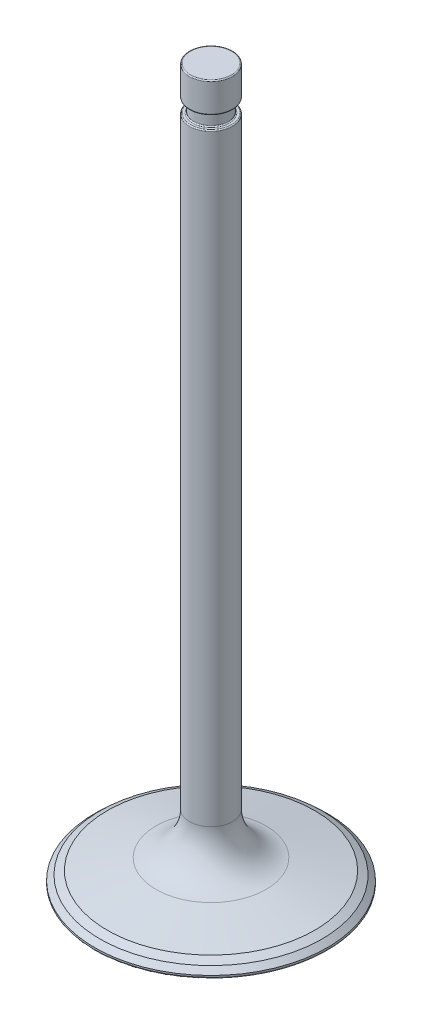
SolidWorks part; units mm, degrees
ref_plane "Front Plane" through (0, 0, 0) normal (0, 0, 1) x (1, 0, 0)
ref_plane "Top Plane" through (0, 0, 0) normal (0, 1, 0) x (1, 0, 0)
ref_plane "Right Plane" through (0, 0, 0) normal (1, 0, 0) x (0, 0, -1)
sketch "Sketch1" plane through (0, 0, 0) normal (0, 0, 1) x (1, 0, 0)
  line L0 (0, 0) -> (0, 165)
  line L1 (0, 0) -> (-27, 0)
  line L2 (-27, 0) -> (-27, 2)
  line L3 (-27, 2) -> (-5, 7)
  line L4 (-5, 7) -> (-5, 155)
  line L5 (-5, 165) -> (0, 165)
  line L6 (-5, 158) -> (-4, 158)
  line L7 (-4, 158) -> (-4, 155)
  line L8 (-4, 155) -> (-5, 155)
  line L9 (-5, 158) -> (-5, 165)
  dimension "D1" = 165
  dimension "D2" = 5
  dimension "D3" = 27
  dimension "D4" = 2
  dimension "D5" = 7
  dimension "D6" = 3
  dimension "D7" = 1
  dimension "D8" = 7
revolve "Revolve1" add sketch "Sketch1" angle 360 about L0
fillet "Fillet1" radius 10 1 edges at (0, 7, -5)
chamfer "Chamfer1" distance 2 angle 30 1 edges at (0, 2, -27) first distance on face at (0, 5.231, -12.7838)
chamfer "Chamfer3" distance 1 angle 15 1 edges at (0, 2.4432, 25.0497) first distance on face at (0, 2.4432, 25.0497)
fillet "Fillet2" radius 0.25 6 edges at (0, 158, -4) (0, 155, -4) (0, 165, -5) (0, 158, -5) (0, 0, -27) (0, 155, -5)
